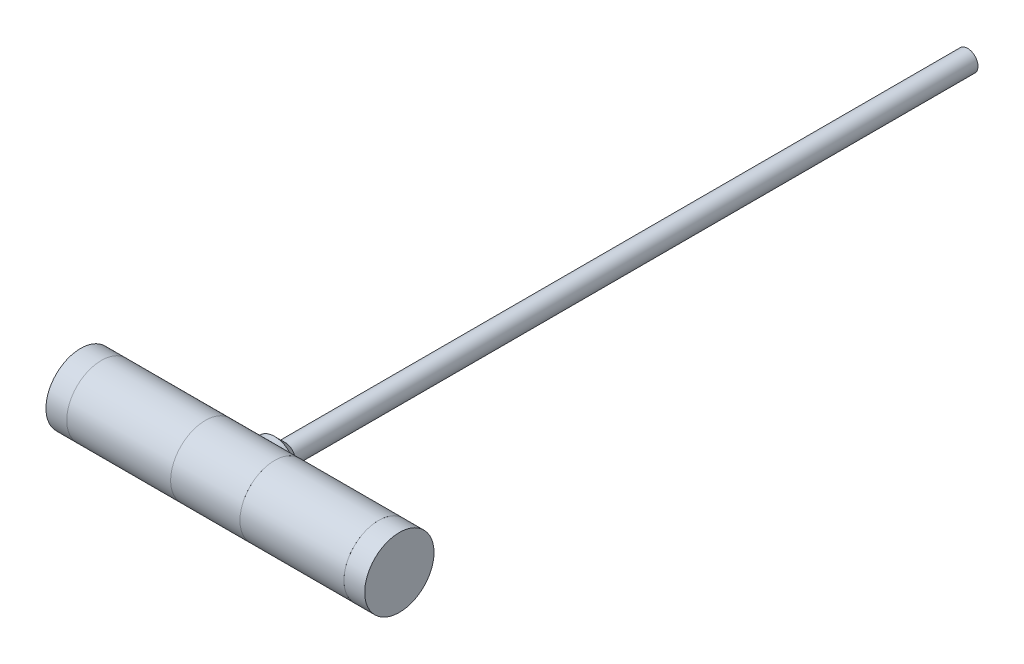
SolidWorks part; units mm, degrees
ref_plane "Front Plane" through (0, 0, 0) normal (0, 0, 1) x (1, 0, 0)
ref_plane "Top Plane" through (0, 0, 0) normal (0, 1, 0) x (1, 0, 0)
ref_plane "Right Plane" through (0, 0, 0) normal (1, 0, 0) x (0, 0, -1)
sketch "Connector Pin Sketch" plane through (0, 0, 0) normal (1, 0, 0) x (0, 0, -1)
  circle A0 centre (0, 0) radius 5
  dimension "D1" = 10
extrude "Outer Pin Extrude 1" add sketch "Connector Pin Sketch" along normal blind 3 from offset 20
extrude "Outer Pin Extrude 2" add sketch "Connector Pin Sketch<2>" against normal blind 3 from offset 20 separate body offset against normal yes
sketch "Connector Pin Sketch<2>" plane through (0, 0, 0) normal (1, 0, 0) x (0, 0, -1) same geometry as "Connector Pin Sketch"
extrude "Middle Pin Extrude 1" add sketch "Connector Pin Sketch<3>" along normal up to surface (20 mm away) from offset 5 separate body up to face at (20, 0, -5)
sketch "Connector Pin Sketch<3>" plane through (0, 0, 0) normal (1, 0, 0) x (0, 0, -1) same geometry as "Connector Pin Sketch"
extrude "Middle Pin Extrude 2" add sketch "Connector Pin Sketch<4>" against normal up to surface (20 mm away) from offset 5 separate body up to face at (-20, 0, -5) offset against normal yes
sketch "Connector Pin Sketch<4>" plane through (0, 0, 0) normal (1, 0, 0) x (0, 0, -1) same geometry as "Connector Pin Sketch"
extrude "Center Pin Extrude" add sketch "Connector Pin Sketch<5>" against normal up to surface (5 mm away) from surface up to face at (-5, 0, -5) starting at face at (5, 0, -5)
sketch "Connector Pin Sketch<5>" plane through (0, 0, 0) normal (1, 0, 0) x (0, 0, -1) same geometry as "Connector Pin Sketch"
sketch "T Joint Sketch" plane through (0, 0, 0) normal (0, 0, 1) x (1, 0, 0)
  circle A0 centre (0, 0) radius 3
  dimension "D1" = 6
extrude "T Joint Extrude" add sketch "T Joint Sketch" against normal blind 5
sketch "Plunger Sketch" plane through (0, 0, -5) normal (0, 0, -1) x (-1, 0, 0)
  circle A0 centre (0, 0) radius 1.5
  dimension "D1" = 3
extrude "Plunger Extrude" add sketch "Plunger Sketch" along normal blind 100
chamfer "Plunger Chamfer" distance 1.5 angle 45 1 edges at (1.5, 0, -5)
